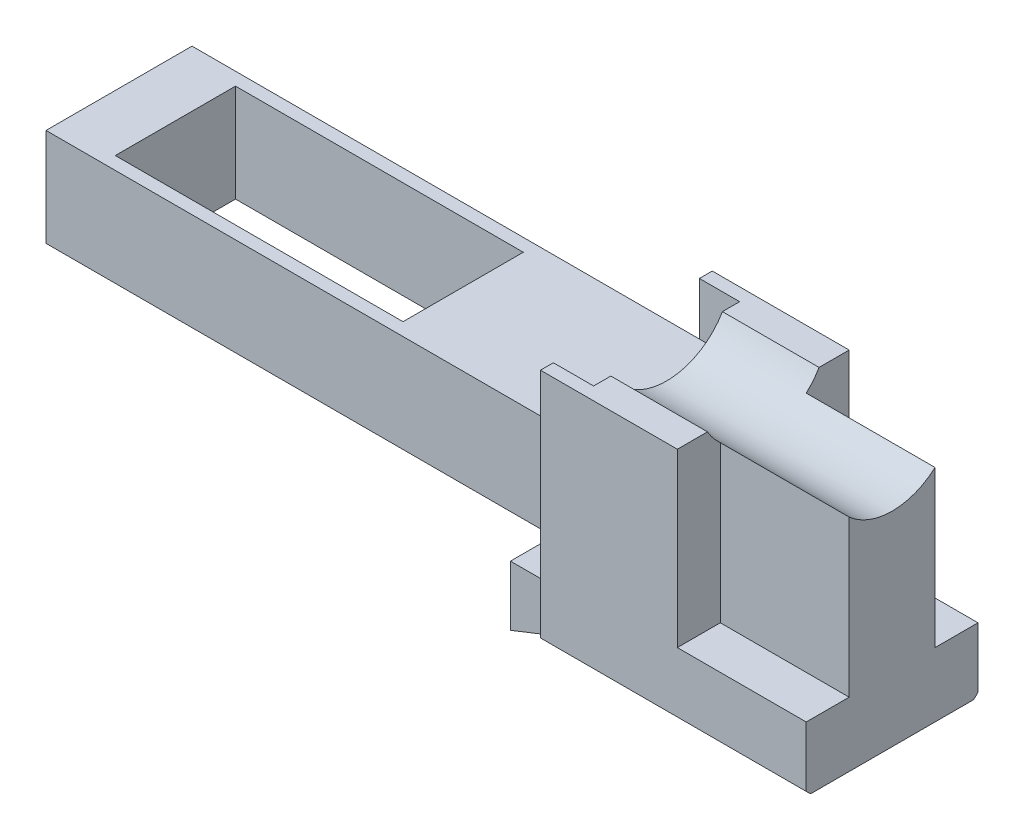
SolidWorks part; units mm, degrees
note: The reader was unsure of these and kept them because the rebuilt part matched: shared geometry of "스케치1<3>".
ref_plane "정면" through (0, 0, 0) normal (0, 0, 1) x (1, 0, 0)
ref_plane "윗면" through (0, 0, 0) normal (0, 1, 0) x (1, 0, 0)
ref_plane "우측면" through (0, 0, 0) normal (1, 0, 0) x (0, 0, -1)
sketch "스케치1" plane through (0, 0, 0) normal (0, 0, 1) x (1, 0, 0)
  line L0 (127.5, 0) -> (180, 0)
  line L1 (180, 0) -> (180, -55)
  line L2 (118.13, -55) -> (180, -55)
  line L3 (108.13, -45) -> (108.13, -58.95)
  line L4 (108.13, -45) -> (118.13, -45)
  line L5 (118.13, -10) -> (118.13, -55)
  line L6 (0, -35) -> (118.13, -35)
  line L7 (0, -35) -> (0, -10)
  line L8 (108.13, -58.95) -> (118.13, -55)
  line L11 (127.5, 0) -> (0, 0)
  line L12 (0, 0) -> (0, -10)
  line L13 (118.13, -10) -> (118.13, 0)
  dimension "D1" = 35
  dimension "D2" = 180
  dimension "D3" = 13.95
  dimension "D4" = 10
  dimension "D5" = 10
  dimension "D6" = 127.5
  dimension "D7" = 55
  dimension "D8" = 118.13
extrude "보스-돌출1" add sketch "스케치1" against normal mid plane 34
extrude "보스-돌출2" add sketch "스케치1<3>" along normal mid plane 40
sketch "스케치1<3>" plane through (0, 0, 0) normal (0, 0, 1) x (1, 0, 0) same geometry as "스케치1"
sketch "스케치2" plane through (0, 0, 0) normal (0, 0, 1) x (1, 0, 0)
  line L1 (0, 0) -> (127.5, 0)
  line L2 (0, 0) -> (0, -12.22)
  line L3 (0, -12.22) -> (127.5, -12.22)
  line L4 (127.5, 0) -> (127.5, -12.22)
  dimension "D1" = 127.5
  dimension "D2" = 12.22
extrude "컷-돌출1" cut sketch "스케치2" against normal mid plane 34
sketch "스케치6" plane through (0, 0, 20) normal (0, 0, 1) x (1, 0, 0)
  line L1 (150, 0) -> (180, 0)
  line L2 (150, 0) -> (150, -40)
  line L3 (150, -40) -> (180, -40)
  line L4 (180, 0) -> (180, -40)
  dimension "D1" = 30
  dimension "D2" = 40
extrude "컷-돌출2" cut sketch "스케치6" against normal blind 10 contours L2 L3 L4 L1
sketch "스케치7" plane through (0, 0, -20) normal (0, 0, -1) x (-1, 0, 0)
  line L1 (-180, 0) -> (-150, 0)
  line L2 (-180, 0) -> (-180, -40)
  line L3 (-180, -40) -> (-150, -40)
  line L4 (-150, 0) -> (-150, -40)
  dimension "D1" = 30
  dimension "D2" = 40
extrude "컷-돌출3" cut sketch "스케치7" against normal blind 10
sketch "스케치8" plane through (0, 0, 0) normal (0, 0, 1) x (1, 0, 0)
  line L0 (0, -35) -> (5.13, -35)
  line L1 (0, -35) -> (118.13, -35) construction
  line L2 (13.13, -12.22) -> (13.13, -35)
  line L3 (118.13, -12.22) -> (127.5, -12.22) construction
  line L4 (5.13, -35) -> (80.13, -35)
  line L5 (5.13, -35) -> (5.13, -12.22)
  line L6 (5.13, -12.22) -> (80.13, -12.22)
  line L7 (80.13, -35) -> (80.13, -12.22)
  dimension "D1" = 5.13
  dimension "D2" = 75
  dimension "D3" = 8
extrude "컷-돌출4" cut sketch "스케치8" against normal mid plane 28 contours L4 L7 L6 L2
sketch "스케치10" plane through (0, 0, 0) normal (0, 0, 1) x (1, 0, 0)
  line L0 (0, 0) -> (5.1, 0) construction
  line L1 (118.13, 0) -> (0, 0) construction
  line L3 (5.1, 0) -> (79.1, 0)
  line L4 (5.1, 0) -> (5.1, -2)
  line L5 (5.1, -2) -> (79.1, -2)
  line L6 (79.1, 0) -> (79.1, -2)
  dimension "D1" = 5.1
  dimension "D2" = 2
  dimension "D3" = 74
sketch "스케치13" plane through (0, 0, 0) normal (0, 0, 1) x (1, 0, 0)
  line L0 (80.13, -16.22) -> (83.13, -19.22)
  line L2 (83.13, -19.22) -> (80.13, -22.22)
  line L3 (80.13, -22.22) -> (80.13, -16.22)
  dimension "D1" = 6
  dimension "D3" = 3
extrude "컷-돌출6" cut sketch "스케치13" against normal mid plane 15
sketch "스케치14" plane through (180, 0, 0) normal (1, 0, 0) x (0, 0, -1)
  line L0 (10, 0) -> (-10, 0) construction
  line L1 (0, 10.4071) -> (0, -10.4071) construction
  line L2 (-5.7582, 0) -> (5.7582, 0) construction
  line L3 (-12.9904, 0) -> (12.9904, 0)
  arc A0 (12.9904, 0) -> (-12.9904, 0) centre (0, 7.5) cw
  point P8 (0, -7.5)
  point P9 (0, 0)
  dimension "D2" = 15
  dimension "D1" = 7.5
extrude "컷-돌출7" cut sketch "스케치14" against normal up to surface (52.5 mm away) up to face at (127.5, -6.11, 0)
chamfer "모따기1" distance 1 angle 45 2 edges at (149.065, -55, 20) (149.065, -55, -20)
